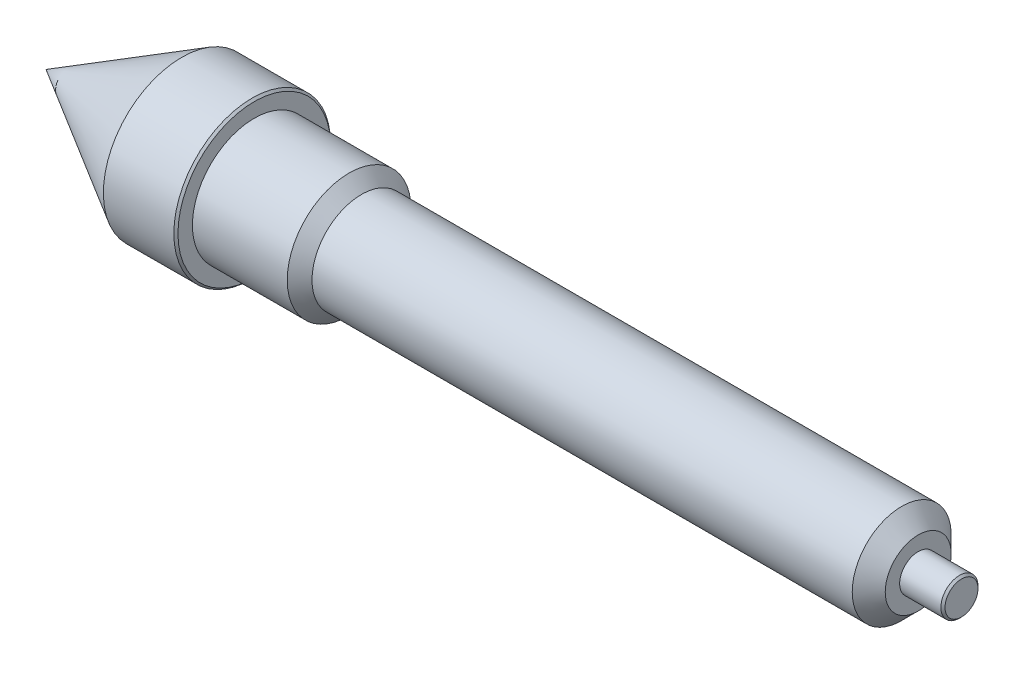
SolidWorks part; units mm, degrees
material "1.2343 (X38CrMoV5-1)"
ref_plane "Płaszczyzna przednia" through (0, 0, 0) normal (0, 0, 1) x (1, 0, 0)
ref_plane "Płaszczyzna górna" through (0, 0, 0) normal (0, 1, 0) x (1, 0, 0)
ref_plane "Płaszczyzna prawa" through (0, 0, 0) normal (1, 0, 0) x (0, 0, -1)
sketch "Szkic5" plane through (0, 0, 0) normal (1, 0, 0) x (0, 0, -1)
  circle A0 centre (0, 0) radius 4.5
extrude "Dodanie-wyciągnięcie4" add sketch "Szkic5" along normal blind 10.5
chamfer "Sfazowanie1" distance 0.5 angle 45 1 edges at (10.5, 0, -4.5)
sketch "Szkic6" plane through (0, 0, 0) normal (-1, 0, 0) x (0, 0, 1)
  circle A0 centre (0, 0) radius 12
  dimension "D1" = 24
extrude "Dodanie-wyciągnięcie5" add sketch "Szkic6" along normal blind 135
chamfer "Sfazowanie2" distance 4 angle 45 1 edges at (0, 0, 12)
sketch "Szkic7" plane through (-135, 0, 0) normal (-1, 0, 0) x (0, 0, 1)
  circle A0 centre (0, 0) radius 15
  dimension "D1" = 30
extrude "Dodanie-wyciągnięcie6" add sketch "Szkic7" along normal blind 26
chamfer "Sfazowanie4" distance 3 angle 45 1 edges at (-135, 0, 15)
sketch "Szkic8" plane through (-161, 0, 0) normal (-1, 0, 0) x (0, 0, 1)
  circle A0 centre (0, 0) radius 19
  dimension "D1" = 38
extrude "Dodanie-wyciągnięcie7" add sketch "Szkic8" along normal blind 17.59
sketch "Szkic10" plane through (0, 0, 0) normal (0, 0, 1) x (1, 0, 0)
  line L0 (-211.499, 0) -> (-178.59, 19)
  line L1 (-178.59, 19) -> (-178.59, 0)
  line L2 (-178.59, 0) -> (-211.499, 0)
  line L3 (-178.59, 0) -> (-161, 0) construction
  line L5 (-178.59, 19) -> (-178.59, -19) construction
  dimension "D1" = 30
  dimension "D2" = 19
  dimension "D3" = 0
  dimension "D4" = 0
revolve "Obrót1" add sketch "Szkic10" angle 360 about L2
chamfer "Sfazowanie5" distance 0.5 angle 45 1 edges at (-161, 0, 19)
